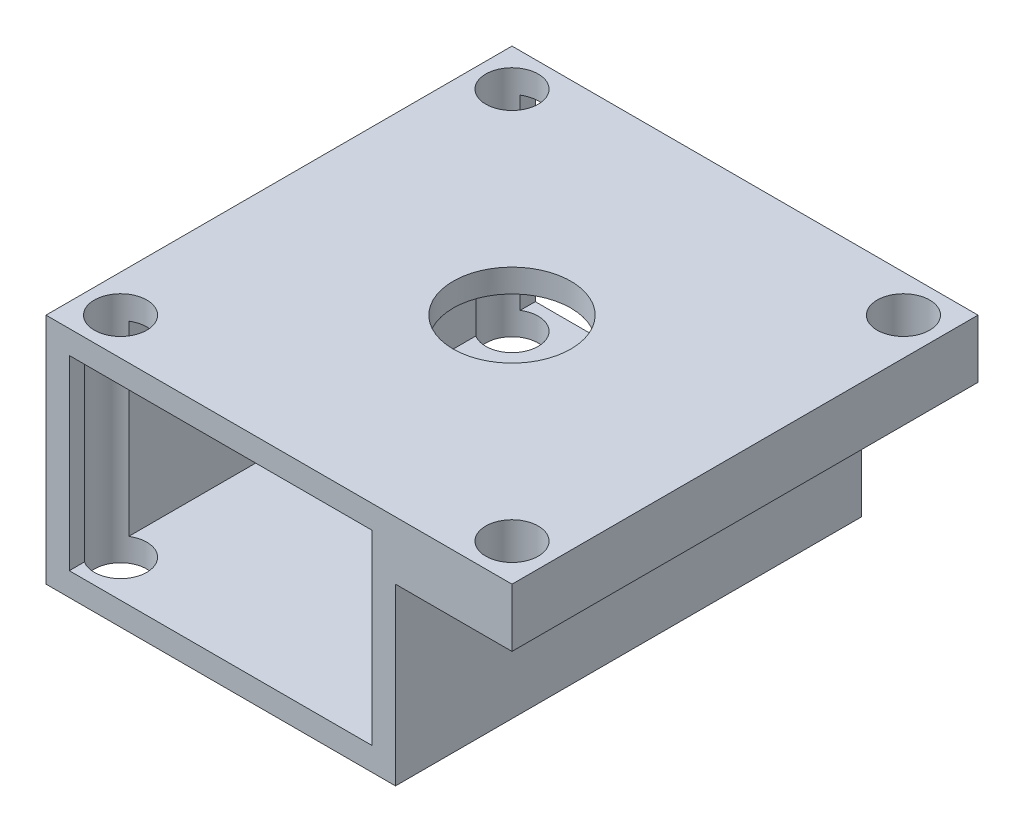
SolidWorks part; units mm, degrees
ref_plane "Front Plane" through (0, 0, 0) normal (0, 0, 1) x (1, 0, 0)
ref_plane "Top Plane" through (0, 0, 0) normal (0, 1, 0) x (1, 0, 0)
ref_plane "Right Plane" through (0, 0, 0) normal (1, 0, 0) x (0, 0, -1)
sketch "Sketch2" plane through (0, 0, 0) normal (0, 1, 0) x (1, 0, 0)
  line L1 (0, 0) -> (38.1, 0)
  line L2 (0, 0) -> (0, 50.8)
  line L3 (0, 50.8) -> (38.1, 50.8)
  line L4 (38.1, 0) -> (38.1, 50.8)
  dimension "D1" = 50.8
  dimension "D2" = 38.1
extrude "Boss-Extrude1" add sketch "Sketch2" along normal blind 25.4
shell "Shell1" thickness 2.54 removed face at (19.05, 12.7, -50.8) removed face at (19.05, 12.7, 0)
sketch "Sketch3" plane through (38.1, 0, 0) normal (1, 0, 0) x (0, 0, -1)
  line L0 (50.8, 25.4) -> (50.8, 0) construction
  line L1 (0, 25.4) -> (50.8, 25.4)
  line L2 (0, 25.4) -> (0, 19.05)
  line L3 (0, 19.05) -> (50.8, 19.05)
  line L4 (50.8, 25.4) -> (50.8, 19.05)
  dimension "D1" = 6.35
extrude "Boss-Extrude2" add sketch "Sketch3" along normal blind 12.7
sketch "Sketch4" plane through (0, 25.4, 0) normal (0, 1, 0) x (1, 0, 0)
  line L0 (0, 50.8) -> (0, 0) construction
  line L1 (50.8, 50.8) -> (0, 50.8) construction
  circle A0 centre (25.4, 25.4) radius 6.4135
  circle A1 centre (4.064, 46.736) radius 2.8575
  circle A2 centre (46.736, 46.736) radius 2.8575
  circle A3 centre (46.736, 4.064) radius 2.8575
  circle A4 centre (4.064, 4.064) radius 2.8575
  dimension "D3" = 12.827
  dimension "D4" = 5.715
  dimension "D1" = 25.4
  dimension "D2" = 25.4
  dimension "D5" = 4.064
  dimension "D6" = 4.064
  dimension "D7" = 4
extrude "Cut-Extrude1" cut sketch "Sketch4" against normal through all
